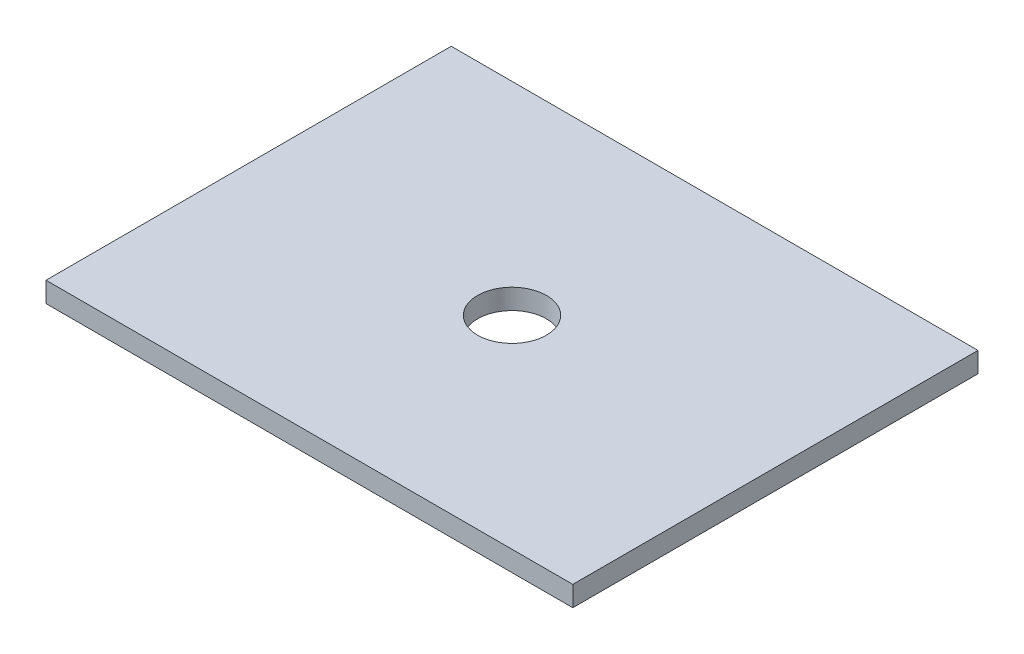
SolidWorks part; units mm, degrees
note: '?' marks a value the reader was unsure of.
ref_plane "Front Plane" through (0, 0, 0) normal (0, 0, 1) x (1, 0, 0)
ref_plane "Top Plane" through (0, 0, 0) normal (0, 1, 0) x (1, 0, 0)
ref_plane "Right Plane" through (0, 0, 0) normal (1, 0, 0) x (0, 0, -1)
sketch "SK_Pad" plane through (0, 0, 0) normal (0, 1, 0) x (1, 0, 0)
  line L1 (-13, 10) -> (13, 10)
  line L2 (-13, 10) -> (-13, -10)
  line L3 (-13, -10) -> (13, -10)
  line L4 (13, 10) -> (13, -10)
  dimension "D1" = 20
  dimension "D2" = 26
  dimension "D3" = 10
  dimension "D4" = 13
base flange "SM_Pad" sketch "SK_Pad" thickness 1 reverse thickness direction no parameters "D1"=1
sketch "SK_Screw" plane through (0, 0, 0) normal (0, 1, 0) x (1, 0, 0)
  circle A0 centre (0, 0) radius 1.7
  dimension "D1" = 3.4
extrude "CUT_Screw" cut sketch "SK_Screw" along normal blind 1
ref_axis "AX_X" through (0, 0, -11) along (0, 0, 1)?
ref_axis "AX_Y" through (14.3, 0, 0) along (-1, 0, 0)?
ref_axis "AX_Z" through (0, 1.05, 0) along (0, -1, 0)?
sketch "Bend-Lines3" [suppressed] plane through (0, 0, 0) normal (0, 1, 0) x (1, 0, 0)
sketch "Bounding-Box3" [suppressed] plane through (0, 0, 0) normal (0, 1, 0) x (1, 0, 0)
sheet metal parameters "Sheet-Metal2" thickness 1 parameters "D1"=1
flat pattern "Flat-Pattern2" [suppressed]
sketch "Bend-Lines4" plane through (0, 0, 0) normal (0, 1, 0) x (1, 0, 0)
sketch "Bounding-Box4" [suppressed] plane through (0, 0, 0) normal (0, 1, 0) x (1, 0, 0)
sheet metal parameters "Sheet-Metal3" thickness 1 parameters "D1"=1
flat pattern "Flat-Pattern2"
sketch "Bend-Lines4" plane through (0, 0, 0) normal (0, 1, 0) x (1, 0, 0)
sketch3d "Bounding-Box4" [suppressed]
  line L0 (13, -10, 0) -> (-13, -10, 0) construction
  line L1 (13, 10, 0) -> (-13, 10, 0) construction
  line L2 (13, -10, 0) -> (13, 10, 0) construction
  line L3 (-13, -10, 0) -> (-13, 10, 0) construction
